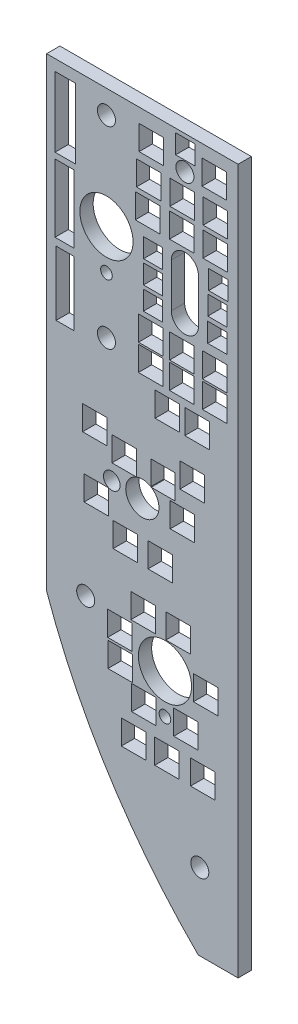
SolidWorks part; units mm, degrees
material "Acrylic (Medium-high impact)"
ref_plane "Front Plane" through (0, 0, 0) normal (0, 0, 1) x (1, 0, 0)
ref_plane "Top Plane" through (0, 0, 0) normal (0, 1, 0) x (1, 0, 0)
ref_plane "Right Plane" through (0, 0, 0) normal (1, 0, 0) x (0, 0, -1)
sketch "Sketch1" plane through (0, 0, 0) normal (0, 0, 1) x (1, 0, 0)
  line L4 (-45.72, 26.9875) -> (-45.72, -84.1375)
  line L5 (-9.525, -141.2875) -> (0, -141.2875)
  line L6 (0, -141.2875) -> (0, 26.9875)
  line L7 (0, 26.9875) -> (-45.72, 26.9875)
  line L8 (-45.72, 26.9875) -> (-45.72, -84.1375)
  line L9 (-9.525, -141.2875) -> (0, -141.2875)
  line L10 (0, -141.2875) -> (0, 26.9875)
  line L11 (0, 26.9875) -> (-45.72, 26.9875)
  arc A1 (-45.72, -84.1375) -> (-9.525, -141.2875) centre (97.9169, -33.2042) ccw
  arc A2 (-45.72, -84.1375) -> (-9.525, -141.2875) centre (97.9169, -33.2042) ccw
  dimension "D1" = 0
extrude "Boss-Extrude1" add sketch "Sketch1" against normal blind 3.175
hole_wizard "1/2 (0.5) Diameter Hole1" positions "Sketch4" profile "Sketch3" hole size "1/2" standard "ANSI Inch" end condition through all
sketch "Sketch4" plane through (0, 0, 0) normal (0, 0, 1) x (1, 0, 0)
  point P0 (-17.4625, -86.5505)
  point P4 (-31.4325, -1.6203)
sketch "Sketch3" plane through (-17.4625, -86.5505, 0) normal (1, 0, 0) x (0, -1, 0)
  line L0 (0, 0) -> (0, 3.175)
  line L1 (0, 3.175) -> (6.35, 3.175)
  line L2 (6.35, 3.175) -> (6.35, 0)
  line L5 (6.35, 0) -> (0, 0)
  line L11 (0, -6.35) -> (0, 107.95) construction
  dimension "Thru Hole Dia." = 12.7
  dimension "Thru Hole Depth" = 3.175
hole_wizard "5/16 (0.3125) Diameter Hole1" positions "Sketch6" profile "Sketch5" hole size "5/16" standard "ANSI Inch" end condition through all
sketch "Sketch6" plane through (0, 0, 0) normal (0, 0, 1) x (1, 0, 0)
  point P0 (-22.86, -53.5305)
sketch "Sketch5" plane through (-22.86, -53.5305, 0) normal (1, 0, 0) x (0, -1, 0)
  line L0 (0, 0) -> (0, 3.175)
  line L1 (0, 3.175) -> (3.9687, 3.175)
  line L2 (3.9687, 3.175) -> (3.9687, 0)
  line L5 (3.9687, 0) -> (0, 0)
  line L11 (0, -6.35) -> (0, 107.95) construction
  dimension "Thru Hole Dia." = 7.9375
  dimension "Thru Hole Depth" = 3.175
hole_wizard "5/32 (0.15625) Diameter Hole1" positions "Sketch8" profile "Sketch7" hole size "5/32" standard "ANSI Inch" end condition through all
sketch "Sketch8" plane through (0, 0, 0) normal (0, 0, 1) x (1, 0, 0)
  line L0 (-22.86, -49.5617) -> (-22.86, -53.5305) construction
  circle A0 centre (-22.86, -53.5305) radius 3.9688 construction
  point P11 (-30.1611, -53.5305)
sketch "Sketch7" plane through (-30.1611, -53.5305, 0) normal (1, 0, 0) x (0, -1, 0)
  line L0 (0, 0) -> (0, 3.175)
  line L1 (0, 3.175) -> (1.9844, 3.175)
  line L2 (1.9844, 3.175) -> (1.9844, 0)
  line L5 (1.9844, 0) -> (0, 0)
  line L11 (0, -6.35) -> (0, 107.95) construction
  dimension "Thru Hole Dia." = 3.9688
  dimension "Thru Hole Depth" = 3.175
hole_wizard "7/64 (0.10938) Diameter Hole1" positions "Sketch10" profile "Sketch9" hole size "7/64" standard "ANSI Inch" end condition through all
sketch "Sketch10" plane through (0, 0, 0) normal (0, 0, 1) x (1, 0, 0)
  point P0 (-17.4646, -95.9667)
  point P3 (-31.4325, -11.1589)
sketch "Sketch9" plane through (-17.4646, -95.9667, 0) normal (1, 0, 0) x (0, -1, 0)
  line L0 (0, 0) -> (0, 3.175)
  line L1 (0, 3.175) -> (1.3891, 3.175)
  line L2 (1.3891, 3.175) -> (1.3891, 0)
  line L5 (1.3891, 0) -> (0, 0)
  line L11 (0, -6.35) -> (0, 107.95) construction
  dimension "Thru Hole Dia." = 2.7783
  dimension "Thru Hole Depth" = 3.175
sketch "Sketch11" plane through (0, 0, -3.175) normal (0, 0, -1) x (-1, 0, 0)
  line L5 (19.8437, -15.24) -> (19.8437, 3.175)
  line L6 (19.8437, 3.175) -> (8.7312, 3.175)
  line L7 (8.7312, 3.175) -> (8.7312, -15.24)
  line L8 (8.7312, -15.24) -> (19.8437, -15.24)
  line L9 (19.8437, -15.24) -> (19.8437, 3.175)
  line L10 (19.8437, 3.175) -> (8.7312, 3.175)
  line L11 (8.7312, 3.175) -> (8.7312, -15.24)
  line L12 (8.7312, -15.24) -> (19.8437, -15.24)
  dimension "D1" = 0
extrude "Cut-Extrude4" [suppressed] cut sketch "Sketch11" against normal through all
hole_wizard "#6 Clearance Hole1" positions "Sketch13" profile "Sketch12" hole size "#6" standard "ANSI Inch" end condition through all
sketch "Sketch13" plane through (0, 0, -3.175) normal (0, 0, -1) x (-1, 0, 0)
  point P0 (12.7, 19.05)
  point P3 (36.3855, -80.4545)
  point P6 (9.144, -122.9995)
  point P10 (31.4325, -24.62)
  point P13 (31.4325, 21.4048)
sketch "Sketch12" plane through (-12.7, 19.05, -3.175) normal (1, 0, 0) x (0, 1, 0)
  line L0 (0, 0) -> (0, 3.175)
  line L1 (0, 3.175) -> (2.1526, 3.175)
  line L2 (2.1526, 3.175) -> (2.1526, 0)
  line L5 (2.1526, 0) -> (0, 0)
  line L11 (0, -6.35) -> (0, 107.95) construction
  dimension "Thru Hole Dia." = 4.3053
  dimension "Thru Hole Depth" = 3.175
hole_wizard "#16 (0.177) Diameter Hole1" positions "Sketch15" profile "Sketch14" hole size "#16" standard "ANSI Inch" end condition through all
sketch "Sketch15" plane through (0, 0, -3.175) normal (0, 0, -1) x (-1, 0, 0)
  line L5 (12.7, 2.794) -> (12.7, -14.859) construction
  line L6 (12.7, -6.0325) -> (17.8753, -6.0325) construction
  point P26 (12.7, -0.7804)
  point P33 (12.7, -11.2846)
sketch "Sketch14" plane through (-12.7, -0.7804, -3.175) normal (1, 0, 0) x (0, 1, 0)
  line L0 (0, 0) -> (0, 3.175)
  line L1 (0, 3.175) -> (2.2479, 3.175)
  line L2 (2.2479, 3.175) -> (2.2479, 0)
  line L5 (2.2479, 0) -> (0, 0)
  line L11 (0, -6.35) -> (0, 107.95) construction
  dimension "Thru Hole Dia." = 4.4958
  dimension "Thru Hole Depth" = 3.175
sketch "Sketch16" plane through (0, 0, -4.775) normal (0, 0, -1) x (-1, 0, 0)
  line L0 (12.7, -11.2846) -> (12.7, -0.7804) construction
  line L1 (2.6659, -22.1354) -> (8.5079, -22.1354)
  line L2 (2.6659, -22.1354) -> (2.6659, -27.9774)
  line L3 (2.6659, -27.9774) -> (8.5079, -27.9774)
  line L4 (8.5079, -22.1354) -> (8.5079, -27.9774)
  line L5 (2.6659, -22.1354) -> (8.5079, -27.9774) construction
  line L6 (2.6659, -27.9774) -> (8.5079, -22.1354) construction
  line L7 (10.5519, -22.1354) -> (16.3939, -22.1354)
  line L8 (10.5519, -22.1354) -> (10.5519, -27.9774)
  line L9 (10.5519, -27.9774) -> (16.3939, -27.9774)
  line L10 (16.3939, -22.1354) -> (16.3939, -27.9774)
  line L11 (10.5519, -22.1354) -> (16.3939, -27.9774) construction
  line L12 (10.5519, -27.9774) -> (16.3939, -22.1354) construction
  line L13 (17.9569, -22.1354) -> (23.7989, -22.1354)
  line L14 (17.9569, -22.1354) -> (17.9569, -27.9774)
  line L15 (17.9569, -27.9774) -> (23.7989, -27.9774)
  line L16 (23.7989, -22.1354) -> (23.7989, -27.9774)
  line L17 (17.9569, -22.1354) -> (23.7989, -27.9774) construction
  line L18 (17.9569, -27.9774) -> (23.7989, -22.1354) construction
  line L19 (17.9319, -15.8614) -> (23.7739, -15.8614)
  line L20 (17.9319, -15.8614) -> (17.9319, -21.7034)
  line L21 (17.9319, -21.7034) -> (23.7739, -21.7034)
  line L22 (23.7739, -15.8614) -> (23.7739, -21.7034)
  line L23 (17.9319, -15.8614) -> (23.7739, -21.7034) construction
  line L24 (17.9319, -21.7034) -> (23.7739, -15.8614) construction
  line L25 (10.5149, -15.8364) -> (16.3569, -15.8364)
  line L26 (10.5149, -15.8364) -> (10.5149, -21.6784)
  line L27 (10.5149, -21.6784) -> (16.3569, -21.6784)
  line L28 (16.3569, -15.8364) -> (16.3569, -21.6784)
  line L29 (10.5149, -15.8364) -> (16.3569, -21.6784) construction
  line L30 (10.5149, -21.6784) -> (16.3569, -15.8364) construction
  line L31 (2.6919, -15.8114) -> (8.5339, -15.8114)
  line L32 (2.6919, -15.8114) -> (2.6919, -21.6534)
  line L33 (2.6919, -21.6534) -> (8.5339, -21.6534)
  line L34 (8.5339, -15.8114) -> (8.5339, -21.6534)
  line L35 (2.6919, -15.8114) -> (8.5339, -21.6534) construction
  line L36 (2.6919, -21.6534) -> (8.5339, -15.8114) construction
  line L41 (39.2165, -27.0307) -> (43.4505, -27.0307)
  line L42 (39.2165, -27.0307) -> (39.2165, -11.6644)
  line L47 (39.2165, -11.6644) -> (43.4505, -11.6644)
  line L48 (43.4505, -27.0307) -> (43.4505, -11.6644)
  line L53 (39.2165, 6.231) -> (43.7187, 6.231)
  line L54 (39.2165, 6.231) -> (39.2165, -9.9754)
  line L55 (39.2165, -9.9754) -> (43.7187, -9.9754)
  line L56 (43.7187, 6.231) -> (43.7187, -9.9754)
  line L57 (38.8582, 7.6135) -> (43.7187, 7.6135)
  line L58 (38.8582, 7.6135) -> (38.8582, 24.3196)
  line L59 (38.8582, 24.3196) -> (43.7187, 24.3196)
  line L60 (43.7187, 7.6135) -> (43.7187, 24.3196)
  line L61 (12.7249, -29.6544) -> (6.8829, -29.6544)
  line L62 (12.7249, -29.6544) -> (12.7249, -35.4964)
  line L63 (12.7249, -35.4964) -> (6.8829, -35.4964)
  line L64 (6.8829, -29.6544) -> (6.8829, -35.4964)
  line L65 (12.7249, -29.6544) -> (6.8829, -35.4964) construction
  line L66 (12.7249, -35.4964) -> (6.8829, -29.6544) construction
  line L67 (19.8109, -29.6034) -> (13.9689, -29.6034)
  line L68 (19.8109, -29.6034) -> (19.8109, -35.4454)
  line L69 (19.8109, -35.4454) -> (13.9689, -35.4454)
  line L70 (13.9689, -29.6034) -> (13.9689, -35.4454)
  line L71 (19.8109, -29.6034) -> (13.9689, -35.4454) construction
  line L72 (19.8109, -35.4454) -> (13.9689, -29.6034) construction
  line L73 (5.5089, -101.4346) -> (11.3509, -101.4346)
  line L74 (5.5089, -101.4346) -> (5.5089, -107.2766)
  line L75 (5.5089, -107.2766) -> (11.3509, -107.2766)
  line L76 (11.3509, -101.4346) -> (11.3509, -107.2766)
  line L77 (5.5089, -101.4346) -> (11.3509, -107.2766) construction
  line L78 (5.5089, -107.2766) -> (11.3509, -101.4346) construction
  line L79 (14.0689, -101.4088) -> (19.9109, -101.4088)
  line L80 (14.0689, -101.4088) -> (14.0689, -107.2508)
  line L81 (14.0689, -107.2508) -> (19.9109, -107.2508)
  line L82 (19.9109, -101.4088) -> (19.9109, -107.2508)
  line L83 (14.0689, -101.4088) -> (19.9109, -107.2508) construction
  line L84 (14.0689, -107.2508) -> (19.9109, -101.4088) construction
  line L85 (22.0469, -101.4342) -> (27.8889, -101.4342)
  line L86 (22.0469, -101.4342) -> (22.0469, -107.2762)
  line L87 (22.0469, -107.2762) -> (27.8889, -107.2762)
  line L88 (27.8889, -101.4342) -> (27.8889, -107.2762)
  line L89 (22.0469, -101.4342) -> (27.8889, -107.2762) construction
  line L90 (22.0469, -107.2762) -> (27.8889, -101.4342) construction
  line L91 (9.5239, -93.1288) -> (15.3659, -93.1288)
  line L92 (9.5239, -93.1288) -> (9.5239, -98.9708)
  line L93 (9.5239, -98.9708) -> (15.3659, -98.9708)
  line L94 (15.3659, -93.1288) -> (15.3659, -98.9708)
  line L95 (9.5239, -93.1288) -> (15.3659, -98.9708) construction
  line L96 (9.5239, -98.9708) -> (15.3659, -93.1288) construction
  line L97 (19.5569, -93.0776) -> (25.3989, -93.0776)
  line L98 (19.5569, -93.0776) -> (19.5569, -98.9196)
  line L99 (19.5569, -98.9196) -> (25.3989, -98.9196)
  line L100 (25.3989, -93.0776) -> (25.3989, -98.9196)
  line L101 (19.5569, -93.0776) -> (25.3989, -98.9196) construction
  line L102 (19.5569, -98.9196) -> (25.3989, -93.0776) construction
  line L103 (4.8249, -83.6546) -> (10.6669, -83.6546)
  line L104 (4.8249, -83.6546) -> (4.8249, -89.4966)
  line L105 (4.8249, -89.4966) -> (10.6669, -89.4966)
  line L106 (10.6669, -83.6546) -> (10.6669, -89.4966)
  line L107 (4.8249, -83.6546) -> (10.6669, -89.4966) construction
  line L108 (4.8249, -89.4966) -> (10.6669, -83.6546) construction
  line L109 (25.2329, -86.9818) -> (31.0749, -86.9818)
  line L110 (25.2329, -86.9818) -> (25.2329, -92.8238)
  line L111 (25.2329, -92.8238) -> (31.0749, -92.8238)
  line L112 (31.0749, -86.9818) -> (31.0749, -92.8238)
  line L113 (25.2329, -86.9818) -> (31.0749, -92.8238) construction
  line L114 (25.2329, -92.8238) -> (31.0749, -86.9818) construction
  line L115 (25.2959, -80.5808) -> (31.1379, -80.5808)
  line L116 (25.2959, -80.5808) -> (25.2959, -86.4228)
  line L117 (25.2959, -86.4228) -> (31.1379, -86.4228)
  line L118 (31.1379, -80.5808) -> (31.1379, -86.4228)
  line L119 (25.2959, -80.5808) -> (31.1379, -86.4228) construction
  line L120 (25.2959, -86.4228) -> (31.1379, -80.5808) construction
  line L121 (19.7609, -74.1546) -> (25.6029, -74.1546)
  line L122 (19.7609, -74.1546) -> (19.7609, -79.9966)
  line L123 (19.7609, -79.9966) -> (25.6029, -79.9966)
  line L124 (25.6029, -74.1546) -> (25.6029, -79.9966)
  line L125 (19.7609, -74.1546) -> (25.6029, -79.9966) construction
  line L126 (19.7609, -79.9966) -> (25.6029, -74.1546) construction
  line L127 (11.4019, -74.1804) -> (17.2439, -74.1804)
  line L128 (11.4019, -74.1804) -> (11.4019, -80.0224)
  line L129 (11.4019, -80.0224) -> (17.2439, -80.0224)
  line L130 (17.2439, -74.1804) -> (17.2439, -80.0224)
  line L131 (11.4019, -74.1804) -> (17.2439, -80.0224) construction
  line L132 (11.4019, -80.0224) -> (17.2439, -74.1804) construction
  line L133 (15.6709, -61.6074) -> (21.5129, -61.6074)
  line L134 (15.6709, -61.6074) -> (15.6709, -67.4494)
  line L135 (15.6709, -67.4494) -> (21.5129, -67.4494)
  line L136 (21.5129, -61.6074) -> (21.5129, -67.4494)
  line L137 (15.6709, -61.6074) -> (21.5129, -67.4494) construction
  line L138 (15.6709, -67.4494) -> (21.5129, -61.6074) construction
  line L139 (24.0019, -61.582) -> (29.8439, -61.582)
  line L140 (24.0019, -61.582) -> (24.0019, -67.424)
  line L141 (24.0019, -67.424) -> (29.8439, -67.424)
  line L142 (29.8439, -61.582) -> (29.8439, -67.424)
  line L143 (24.0019, -61.582) -> (29.8439, -67.424) construction
  line L144 (24.0019, -67.424) -> (29.8439, -61.582) construction
  line L145 (30.9369, -55.4098) -> (36.7789, -55.4098)
  line L146 (30.9369, -55.4098) -> (30.9369, -61.2518)
  line L147 (30.9369, -61.2518) -> (36.7789, -61.2518)
  line L148 (36.7789, -55.4098) -> (36.7789, -61.2518)
  line L149 (30.9369, -55.4098) -> (36.7789, -61.2518) construction
  line L150 (30.9369, -61.2518) -> (36.7789, -55.4098) construction
  line L151 (10.3599, -50.66) -> (16.2019, -50.66)
  line L152 (10.3599, -50.66) -> (10.3599, -56.502)
  line L153 (10.3599, -56.502) -> (16.2019, -56.502)
  line L154 (16.2019, -50.66) -> (16.2019, -56.502)
  line L155 (10.3599, -50.66) -> (16.2019, -56.502) construction
  line L156 (10.3599, -56.502) -> (16.2019, -50.66) construction
  line L157 (8.0509, -41.2874) -> (13.8929, -41.2874)
  line L158 (8.0509, -41.2874) -> (8.0509, -47.1294)
  line L159 (8.0509, -47.1294) -> (13.8929, -47.1294)
  line L160 (13.8929, -41.2874) -> (13.8929, -47.1294)
  line L161 (8.0509, -41.2874) -> (13.8929, -47.1294) construction
  line L162 (8.0509, -47.1294) -> (13.8929, -41.2874) construction
  line L163 (15.0109, -44.3354) -> (20.8529, -44.3354)
  line L164 (15.0109, -44.3354) -> (15.0109, -50.1774)
  line L165 (15.0109, -50.1774) -> (20.8529, -50.1774)
  line L166 (20.8529, -44.3354) -> (20.8529, -50.1774)
  line L167 (15.0109, -44.3354) -> (20.8529, -50.1774) construction
  line L168 (15.0109, -50.1774) -> (20.8529, -44.3354) construction
  line L169 (24.2819, -43.9798) -> (30.1239, -43.9798)
  line L170 (24.2819, -43.9798) -> (24.2819, -49.8218)
  line L171 (24.2819, -49.8218) -> (30.1239, -49.8218)
  line L172 (30.1239, -43.9798) -> (30.1239, -49.8218)
  line L173 (24.2819, -43.9798) -> (30.1239, -49.8218) construction
  line L174 (24.2819, -49.8218) -> (30.1239, -43.9798) construction
  line L175 (31.2919, -41.0588) -> (37.1339, -41.0588)
  line L176 (31.2919, -41.0588) -> (31.2919, -46.9008)
  line L177 (31.2919, -46.9008) -> (37.1339, -46.9008)
  line L178 (37.1339, -41.0588) -> (37.1339, -46.9008)
  line L179 (31.2919, -41.0588) -> (37.1339, -46.9008) construction
  line L180 (31.2919, -46.9008) -> (37.1339, -41.0588) construction
  line L185 (9.4609, -11.2846) -> (9.4609, -0.7804)
  line L186 (15.9391, -11.2846) -> (15.9391, -0.7804)
  line L193 (2.6809, -9.0944) -> (7.2529, -9.0944)
  line L194 (2.6809, -9.0944) -> (2.6809, -13.6664)
  line L195 (2.6809, -13.6664) -> (7.2529, -13.6664)
  line L196 (7.2529, -9.0944) -> (7.2529, -13.6664)
  line L197 (2.6809, -9.0944) -> (7.2529, -13.6664) construction
  line L198 (2.6809, -13.6664) -> (7.2529, -9.0944) construction
  line L199 (2.6659, -3.4664) -> (7.2379, -3.4664)
  line L200 (2.6659, -3.4664) -> (2.6659, -8.0384)
  line L201 (2.6659, -8.0384) -> (7.2379, -8.0384)
  line L202 (7.2379, -3.4664) -> (7.2379, -8.0384)
  line L203 (2.6659, -3.4664) -> (7.2379, -8.0384) construction
  line L204 (2.6659, -8.0384) -> (7.2379, -3.4664) construction
  line L205 (2.4609, 1.9176) -> (7.0329, 1.9176)
  line L206 (2.4609, 1.9176) -> (2.4609, -2.6544)
  line L207 (2.4609, -2.6544) -> (7.0329, -2.6544)
  line L208 (7.0329, 1.9176) -> (7.0329, -2.6544)
  line L209 (2.4609, 1.9176) -> (7.0329, -2.6544) construction
  line L210 (2.4609, -2.6544) -> (7.0329, 1.9176) construction
  line L211 (2.5389, 9.2076) -> (8.3809, 9.2076)
  line L212 (2.5389, 9.2076) -> (2.5389, 3.3656)
  line L213 (2.5389, 3.3656) -> (8.3809, 3.3656)
  line L214 (8.3809, 9.2076) -> (8.3809, 3.3656)
  line L215 (2.5389, 9.2076) -> (8.3809, 3.3656) construction
  line L216 (2.5389, 3.3656) -> (8.3809, 9.2076) construction
  line L217 (10.5379, 9.1566) -> (16.3799, 9.1566)
  line L218 (10.5379, 9.1566) -> (10.5379, 3.3146)
  line L219 (10.5379, 3.3146) -> (16.3799, 3.3146)
  line L220 (16.3799, 9.1566) -> (16.3799, 3.3146)
  line L221 (10.5379, 9.1566) -> (16.3799, 3.3146) construction
  line L222 (10.5379, 3.3146) -> (16.3799, 9.1566) construction
  line L223 (18.7049, 9.0556) -> (24.5469, 9.0556)
  line L224 (18.7049, 9.0556) -> (18.7049, 3.2136)
  line L225 (18.7049, 3.2136) -> (24.5469, 3.2136)
  line L226 (24.5469, 9.0556) -> (24.5469, 3.2136)
  line L227 (18.7049, 9.0556) -> (24.5469, 3.2136) construction
  line L228 (18.7049, 3.2136) -> (24.5469, 9.0556) construction
  line L229 (17.9969, 0.7356) -> (22.5689, 0.7356)
  line L230 (17.9969, 0.7356) -> (17.9969, -3.8364)
  line L231 (17.9969, -3.8364) -> (22.5689, -3.8364)
  line L232 (22.5689, 0.7356) -> (22.5689, -3.8364)
  line L233 (17.9969, 0.7356) -> (22.5689, -3.8364) construction
  line L234 (17.9969, -3.8364) -> (22.5689, 0.7356) construction
  line L235 (18.0219, -4.6994) -> (22.5939, -4.6994)
  line L236 (18.0219, -4.6994) -> (18.0219, -9.2714)
  line L237 (18.0219, -9.2714) -> (22.5939, -9.2714)
  line L238 (22.5939, -4.6994) -> (22.5939, -9.2714)
  line L239 (18.0219, -4.6994) -> (22.5939, -9.2714) construction
  line L240 (18.0219, -9.2714) -> (22.5939, -4.6994) construction
  line L241 (18.0479, -10.1354) -> (22.6199, -10.1354)
  line L242 (18.0479, -10.1354) -> (18.0479, -14.7074)
  line L243 (18.0479, -14.7074) -> (22.6199, -14.7074)
  line L244 (22.6199, -10.1354) -> (22.6199, -14.7074)
  line L245 (18.0479, -10.1354) -> (22.6199, -14.7074) construction
  line L246 (18.0479, -14.7074) -> (22.6199, -10.1354) construction
  line L247 (2.4859, 16.0666) -> (8.3279, 16.0666)
  line L248 (2.4859, 16.0666) -> (2.4859, 10.2246)
  line L249 (2.4859, 10.2246) -> (8.3279, 10.2246)
  line L250 (8.3279, 16.0666) -> (8.3279, 10.2246)
  line L251 (2.4859, 16.0666) -> (8.3279, 10.2246) construction
  line L252 (2.4859, 10.2246) -> (8.3279, 16.0666) construction
  line L253 (10.4389, 15.9896) -> (16.2809, 15.9896)
  line L254 (10.4389, 15.9896) -> (10.4389, 10.1476)
  line L255 (10.4389, 10.1476) -> (16.2809, 10.1476)
  line L256 (16.2809, 15.9896) -> (16.2809, 10.1476)
  line L257 (10.4389, 15.9896) -> (16.2809, 10.1476) construction
  line L258 (10.4389, 10.1476) -> (16.2809, 15.9896) construction
  line L259 (18.4399, 15.9896) -> (24.2819, 15.9896)
  line L260 (18.4399, 15.9896) -> (18.4399, 10.1476)
  line L261 (18.4399, 10.1476) -> (24.2819, 10.1476)
  line L262 (24.2819, 15.9896) -> (24.2819, 10.1476)
  line L263 (18.4399, 15.9896) -> (24.2819, 10.1476) construction
  line L264 (18.4399, 10.1476) -> (24.2819, 15.9896) construction
  line L265 (17.8049, 23.6096) -> (23.6469, 23.6096)
  line L266 (17.8049, 23.6096) -> (17.8049, 17.7676)
  line L267 (17.8049, 17.7676) -> (23.6469, 17.7676)
  line L268 (23.6469, 23.6096) -> (23.6469, 17.7676)
  line L269 (17.8049, 23.6096) -> (23.6469, 17.7676) construction
  line L270 (17.8049, 17.7676) -> (23.6469, 23.6096) construction
  line L271 (2.7659, 23.9906) -> (8.6079, 23.9906)
  line L272 (2.7659, 23.9906) -> (2.7659, 18.1486)
  line L273 (2.7659, 18.1486) -> (8.6079, 18.1486)
  line L274 (8.6079, 23.9906) -> (8.6079, 18.1486)
  line L275 (2.7659, 23.9906) -> (8.6079, 18.1486) construction
  line L276 (2.7659, 18.1486) -> (8.6079, 23.9906) construction
  line L277 (10.3369, 26.0476) -> (14.9089, 26.0476)
  line L278 (10.3369, 26.0476) -> (10.3369, 21.4756)
  line L279 (10.3369, 21.4756) -> (14.9089, 21.4756)
  line L280 (14.9089, 26.0476) -> (14.9089, 21.4756)
  line L281 (10.3369, 26.0476) -> (14.9089, 21.4756) construction
  line L282 (10.3369, 21.4756) -> (14.9089, 26.0476) construction
  arc A0 (9.4609, -11.2846) -> (15.9391, -11.2846) centre (12.7, -11.2846) ccw
  arc A1 (15.9391, -0.7804) -> (9.4609, -0.7804) centre (12.7, -0.7804) ccw
  point P0 (5.5869, -25.0564)
  point P6 (13.4729, -25.0564)
  point P12 (20.8779, -25.0564)
  point P18 (20.8529, -18.7824)
  point P24 (13.4359, -18.7574)
  point P30 (5.6129, -18.7324)
  point P50 (9.8039, -32.5754)
  point P57 (16.8899, -32.5244)
  point P63 (8.4299, -104.3556)
  point P69 (16.9899, -104.3298)
  point P75 (24.9679, -104.3552)
  point P81 (12.4449, -96.0498)
  point P87 (22.4779, -95.9986)
  point P93 (7.7459, -86.5756)
  point P99 (28.1539, -89.9028)
  point P105 (28.2169, -83.5018)
  point P111 (22.6819, -77.0756)
  point P117 (14.3229, -77.1014)
  point P123 (18.5919, -64.5284)
  point P129 (26.9229, -64.503)
  point P135 (33.8579, -58.3308)
  point P141 (13.2809, -53.581)
  point P147 (10.9719, -44.2084)
  point P153 (17.9319, -47.2564)
  point P159 (27.2029, -46.9008)
  point P165 (34.2129, -43.9798)
  point P173 (12.7, -6.0325)
  point P183 (4.9669, -11.3804)
  point P189 (4.9519, -5.7524)
  point P195 (4.7469, -0.3684)
  point P201 (5.4599, 6.2866)
  point P207 (13.4589, 6.2356)
  point P213 (21.6259, 6.1346)
  point P219 (20.2829, -1.5504)
  point P225 (20.3079, -6.9854)
  point P231 (20.3339, -12.4214)
  point P237 (5.4069, 13.1456)
  point P243 (13.3599, 13.0686)
  point P249 (21.3609, 13.0686)
  point P255 (20.7259, 20.6886)
  point P261 (5.6869, 21.0696)
  point P267 (12.6229, 23.7616)
  point P273 (19.9109, -104.3298)
  dimension "D1" = 5.842
  dimension "D2" = 5.842
  dimension "D3" = 4.572
extrude "Cut-Extrude5" cut sketch "Sketch16" against normal through all
